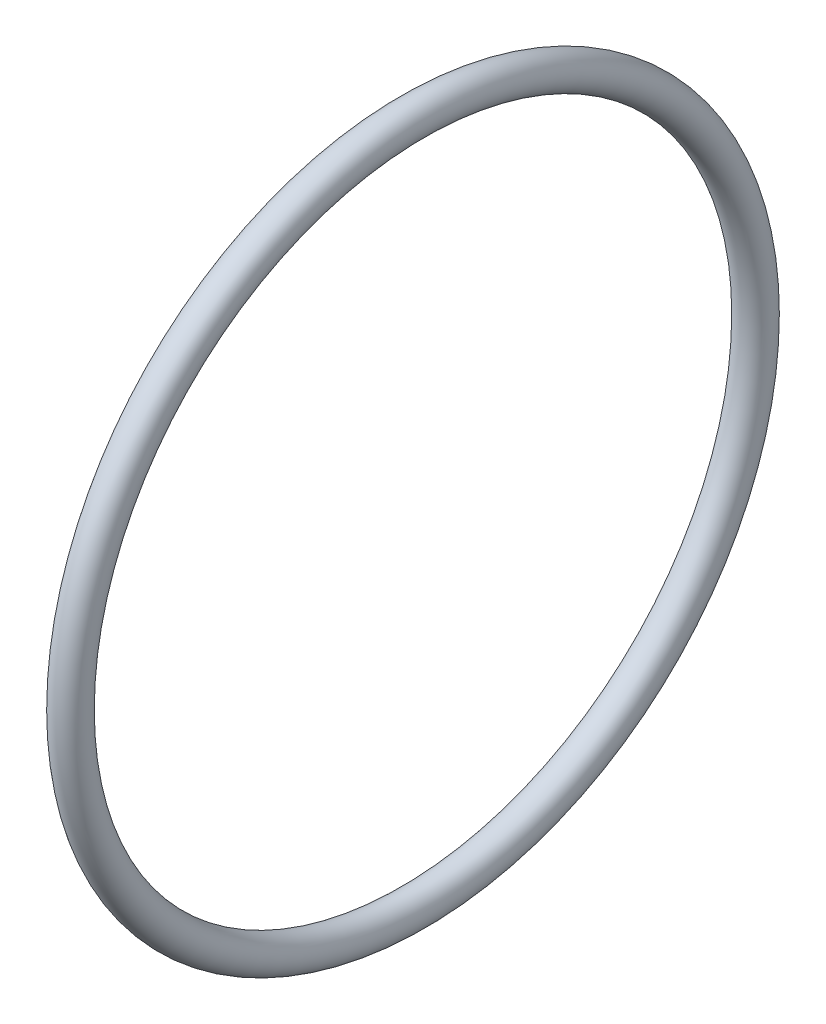
SolidWorks part; units mm, degrees
ref_plane "plan de coupe" through (0, 0, 0) normal (0, 0, 1) x (1, 0, 0)
ref_plane "Plane2" through (0, 0, 0) normal (0, 1, 0) x (1, 0, 0)
ref_plane "Plane3" through (0, 0, 0) normal (1, 0, 0) x (0, 0, -1)
sketch "Esquisse1" plane through (0, 0, 0) normal (0, 0, 1) x (1, 0, 0)
  circle A0 centre (0, 0) radius 0.75
  dimension "D1" = 1.5
sketch "Esquisse2" plane through (0, 0, 0) normal (1, 0, 0) x (0, 0, -1)
  circle A0 centre (0, -15.25) radius 14.5
  dimension "D1" = 29
sweep "joint" add profiles "Esquisse1" path "Esquisse2"
ref_plane "Plan4" through (0, -15.25, 0) normal (0, 1, 0) x (-1, 0, 0)
ref_axis "Axe3" through (-104.7559, -15.25, 0) along (1, 0, 0)
